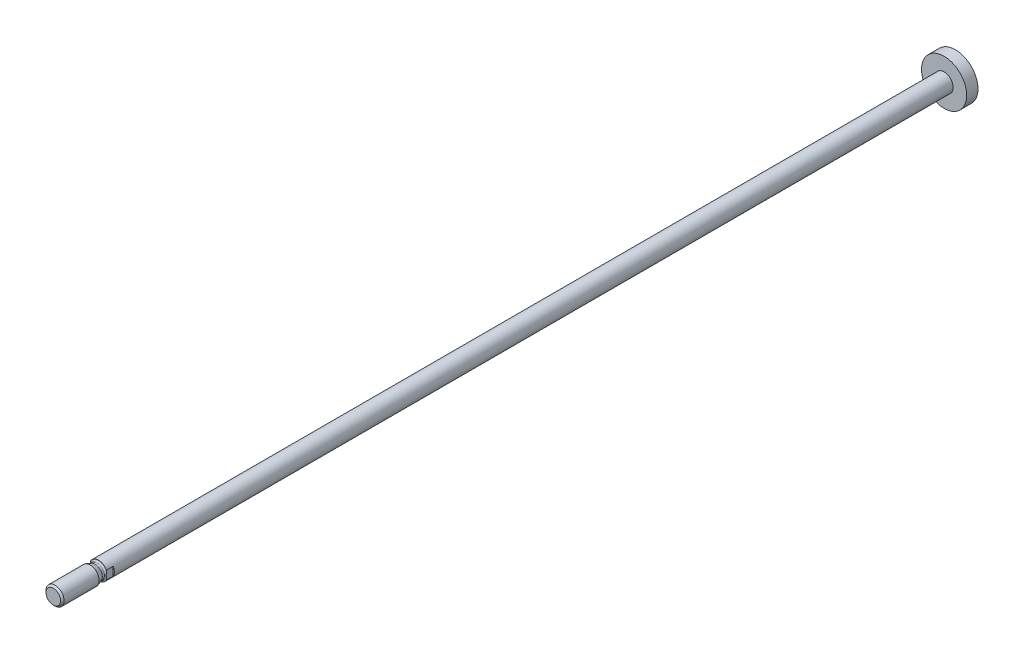
SolidWorks part; units mm, degrees
ref_plane "Ebene vorne" through (0, 0, 0) normal (0, 0, 1) x (1, 0, 0)
ref_plane "Ebene oben" through (0, 0, 0) normal (0, 1, 0) x (1, 0, 0)
ref_plane "Ebene rechts" through (0, 0, 0) normal (1, 0, 0) x (0, 0, -1)
sketch "Skizze1" plane through (0, 0, 0) normal (1, 0, 0) x (0, 0, -1)
  line L0 (-4, 0) -> (-4, 4)
  line L1 (-4, 4) -> (370.3, 4)
  line L2 (370.3, 4) -> (370.3, 10)
  line L3 (370.3, 10) -> (375.3, 10)
  line L4 (375.3, 10) -> (375.3, 0)
  line L5 (375.3, 0) -> (-4, 0)
  line L6 (375.3, 0) -> (-4, 0) construction
revolve "Rotation1" add sketch "Skizze1" angle 360 about L6 reverse direction yes
sketch "Skizze2" plane through (0, 0, 0) normal (1, 0, 0) x (0, 0, -1)
  line L0 (-24, 0) -> (-24, 3.233)
  line L1 (-24, 3.233) -> (-23.233, 4)
  line L2 (-23.233, 4) -> (-7.698, 4)
  line L3 (-7.698, 4) -> (-5.5994, 3.2362)
  line L4 (-5.3942, 3.2) -> (-4.6, 3.2)
  line L5 (-4, 3.8) -> (-4, 4)
  line L6 (-4, 4) -> (-3, 4)
  line L7 (-3, 4) -> (-3, 0)
  line L8 (-3, 0) -> (-24, 0)
  line L9 (-3, 0) -> (-24, 0) construction
  arc A0 (-5.5994, 3.2362) -> (-5.3942, 3.2) centre (-5.3942, 3.8) ccw
  arc A1 (-4.6, 3.2) -> (-4, 3.8) centre (-4.6, 3.8) ccw
revolve "Rotation2" add sketch "Skizze2" angle 360 about L9 reverse direction yes
cosmetic thread "Gewindedarstellung1" parameters "D1"=16.302, "D2"=6.466
ref_plane "Ebene1" through (0, 0, 4) normal (0, 0, 1) x (1, 0, 0)
ref_plane "Ebene2" through (0, 0, 1) normal (0, 0, 1) x (1, 0, 0)
sketch "Skizze3" plane through (0, 0, 1) normal (0, 0, 1) x (1, 0, 0)
  line L0 (-7, 14) -> (-7, -7)
  line L1 (-7, -7) -> (-3.5, -7)
  line L2 (-3.5, -7) -> (-3.5, 7)
  line L3 (-3.5, 7) -> (3.5, 7)
  line L4 (3.5, 7) -> (3.5, -7)
  line L5 (3.5, -7) -> (7, -7)
  line L6 (7, -7) -> (7, 14)
  line L7 (7, 14) -> (-7, 14)
extrude "Schnitt-Linear austragen1" cut sketch "Skizze3" along normal blind 4
ref_plane "Ebene3" through (0, 0, -752) normal (0, 0, 1) x (1, 0, 0)
ref_plane "Ebene4" through (0, 0, 20) normal (0, 0, 1) x (1, 0, 0)
ref_plane "Ebene5" through (0, 0, 12) normal (0, 0, 1) x (1, 0, 0)
ref_plane "FDT_KSAUFSATZ XY" through (0, 0, 12) normal (0, 0, 1) x (1, 0, 0)
ref_plane "FDT_KSAUFSATZ XZ" through (0, 0, 0) normal (0, 1, 0) x (1, 0, 0)
ref_plane "FDT_KSAUFSATZ YZ" through (0, 0, 0) normal (-1, 0, 0) x (0, 0, 1)
ref_axis "FDT_KSAUFSATZ X" through (80.9, 0, 12) along (-1, 0, 0)
ref_axis "FDT_KSAUFSATZ Y" through (0, 50, 12) along (0, -1, 0)
ref_axis "FDT_KSAUFSATZ Z" through (0, 0, 80.9) along (0, 0, -1)
sketch3d "FDT_KSAUFSATZ"
  point P0 (0, 0, 12)
ref_plane "FDT_NUT XY" through (0, 0, 12) normal (0, 0, 1) x (1, 0, 0)
ref_plane "FDT_NUT XZ" through (0, 0, 0) normal (0, 1, 0) x (1, 0, 0)
ref_plane "FDT_NUT YZ" through (0, 0, 0) normal (-1, 0, 0) x (0, 0, 1)
ref_axis "FDT_NUT X" through (80.9, 0, 12) along (-1, 0, 0)
ref_axis "FDT_NUT Y" through (0, 50, 12) along (0, -1, 0)
ref_axis "FDT_NUT Z" through (0, 0, 80.9) along (0, 0, -1)
sketch3d "FDT_NUT"
  point P0 (0, 0, 12)
ref_plane "KS XY" through (0, 0, 0) normal (0, 0, -1) x (-1, 0, 0)
ref_plane "KS XZ" through (0, 0, 0) normal (0, 1, 0) x (1, 0, 0)
ref_plane "KS YZ" through (0, 0, 0) normal (1, 0, 0) x (0, 0, -1)
ref_axis "KS X" through (-80.9, 0, 0) along (1, 0, 0)
ref_axis "KS Y" through (0, 50, 0) along (0, -1, 0)
ref_axis "KS Z" through (0, 0, -80.9) along (0, 0, 1)
sketch3d "KS"
  point P0 (0, 0, 0)
ref_plane "NUT1 XY" through (0, 0, 20) normal (0, 0, 1) x (1, 0, 0)
ref_plane "NUT1 XZ" through (0, 0, 0) normal (0, -1, 0) x (-1, 0, 0)
ref_plane "NUT1 YZ" through (0, 0, 0) normal (1, 0, 0) x (0, 0, -1)
ref_axis "NUT1 X" through (-80.9, 0, 20) along (1, 0, 0)
ref_axis "NUT1 Y" through (0, -50, 20) along (0, 1, 0)
ref_axis "NUT1 Z" through (0, 0, 80.9) along (0, 0, -1)
sketch3d "NUT1"
  point P0 (0, 0, 20)
